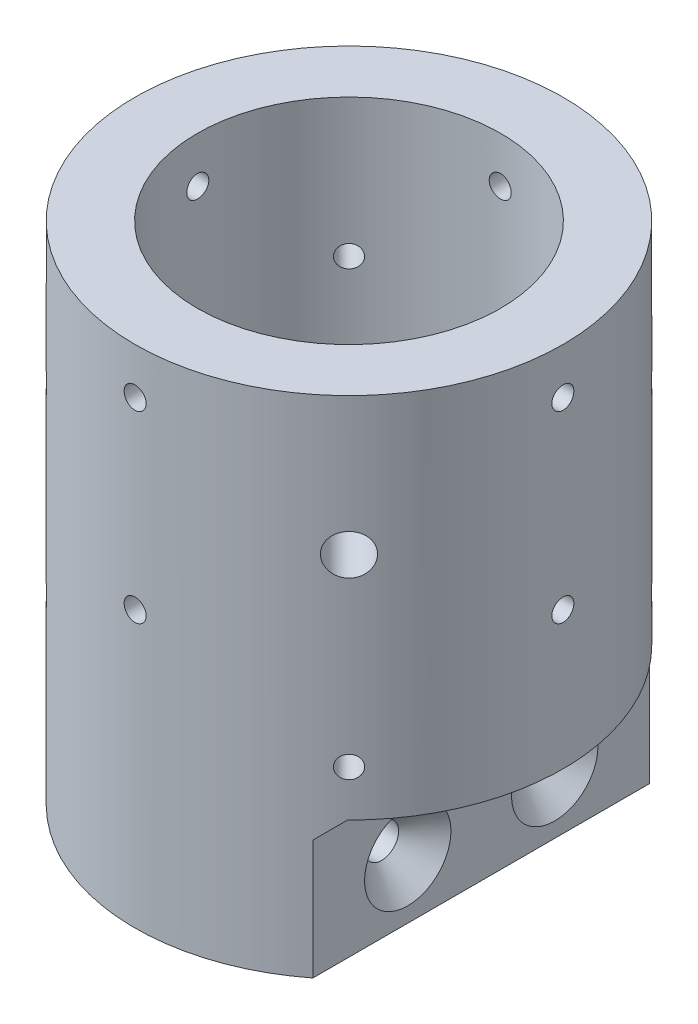
SolidWorks part; units mm, degrees
ref_plane "Спереди" through (0, 0, 0) normal (0, 0, 1) x (1, 0, 0)
ref_plane "Сверху" through (0, 0, 0) normal (0, 1, 0) x (1, 0, 0)
ref_plane "Справа" through (0, 0, 0) normal (1, 0, 0) x (0, 0, -1)
sketch "Эскиз1" plane through (0, 0, 0) normal (0, 1, 0) x (1, 0, 0)
  circle A0 centre (0, 0) radius 23.3
  dimension "D1" = 46.6
extrude "Бобышка-Вытянуть1" add sketch "Эскиз1" along normal blind 5
sketch "Эскиз2" plane through (0, 5, 0) normal (0, 1, 0) x (1, 0, 0)
  circle A0 centre (0, 0) radius 23.3
  circle A1 centre (0, 0) radius 16.5
  circle A2 centre (0, 0) radius 23.3 construction
  dimension "D1" = 33
  dimension "D2" = 0
extrude "Бобышка-Вытянуть2" add sketch "Эскиз2" along normal blind 35
chamfer "Фаска8" distance 2 angle 45 1 edges at (0, 5, 16.5)
sketch "Эскиз3" plane through (0, 0, 0) normal (1, 0, 0) x (0, 0, -1)
  line L0 (-23.3, 20) -> (28.0263, 20) construction
  line L1 (-23.3, 40) -> (-23.3, 0) construction
  line L2 (16.5, 40) -> (-16.5, 40) construction
  circle A1 centre (0, 35) radius 1.2
  dimension "D1" = 2.4
  dimension "D2" = 5
extrude "Вырез-Вытянуть1" cut sketch "Эскиз3" against normal through all
ref_plane "Плоскость1" through (0, 0, 0) normal (0.7071, 0, 0.7071) x (0, -1, 0)
sketch "Эскиз4" plane through (0, 0, 0) normal (0.7071, 0, 0.7071) x (0, -1, 0)
  line L0 (-20, 23.3) -> (-20, -30.0625) construction
  line L1 (0, 23.3) -> (-40, 23.3) construction
  line L3 (0, -23.3) -> (0, 23.3) construction
  circle A1 centre (-5, 0) radius 1.2
  dimension "D1" = 5
  dimension "D2" = 2.4
extrude "Вырез-Вытянуть2" cut sketch "Эскиз4" against normal through all from offset 16.3 offset against normal yes
pattern_circular "Круговой массив1" count 4 over 360 about axis through (0, 5, 0) along (0, -1, 0) of "Вырез-Вытянуть2"
pattern_circular "Круговой массив2" count 4 over 360 about axis through (0, 5, 0) along (0, -1, 0) of "Вырез-Вытянуть1"
pattern_linear "Линейный массив3" count 2 spacing 20 along (0, 1, 0) of "Круговой массив1"
pattern_linear "Линейный массив4" count 2 spacing 20 along (0, -1, 0) of "Круговой массив2"
sketch "Эскиз12" plane through (0, 0, 0) normal (0, -1, 0) x (1, 0, 0)
  line L1 (14.3923, 18.3235) -> (14.3923, -18.3235)
  line L20 (0, 15) -> (-2.7835, 17.7835)
  line L21 (-2.7835, -17.7835) -> (0, -15)
  line L22 (0, -15) -> (0, 15)
  line L23 (0, 15) -> (-2.7835, 17.7835)
  line L24 (-2.7835, -17.7835) -> (0, -15)
  line L25 (0, -15) -> (0, 15)
  circle A6 centre (0, 0) radius 23.3 construction
  arc A7 (14.3923, 18.3235) -> (14.3923, -18.3235) centre (0, 0) ccw
  arc A13 (-2.7835, 17.7835) -> (-2.7835, -17.7835) centre (0, 0) ccw
  arc A14 (-2.7835, 17.7835) -> (-2.7835, -17.7835) centre (0, 0) ccw
  dimension "D1" = 0
extrude "Бобышка-Вытянуть3" add sketch "Эскиз12" along normal blind 15 contours L1 region at (13.7929, 0, 0)
sketch "Эскиз13" plane through (0, -15, 0) normal (0, -1, 0) x (1, 0, 0)
  line L14 (-2.6786, -18.1029) -> (0.3, -15.1243)
  line L15 (0.3, 15.1243) -> (-2.6786, 18.1029)
  line L16 (0.3, -15.1243) -> (0.3, 15.1243)
  line L17 (-2.6786, -18.1029) -> (0.3, -15.1243)
  line L18 (0.3, 15.1243) -> (-2.6786, 18.1029)
  line L19 (0.3, -15.1243) -> (0.3, 15.1243)
  arc A5 (-2.6786, 18.1029) -> (-2.6786, -18.1029) centre (0, 0) ccw
  arc A6 (-2.6786, 18.1029) -> (-2.6786, -18.1029) centre (0, 0) ccw
  dimension "D1" = 0.3
extrude "Вырез-Вытянуть10" cut sketch "Эскиз13" against normal up to surface (15 mm away) up to face at (18.8461, 0, 0)
chamfer "Фаска4" distance 2 angle 45 1 edges at (14.3923, 0, 0)
chamfer "Фаска6" distance 2 angle 45 4 edges at (-1.1893, 0, -16.6136) (-18.3, 0, 0) (0.3, 0, 0) (-1.1893, 0, 16.6136)
chamfer "Фаска7" distance 2 angle 45 4 edges at (-1.1893, -15, -16.6136) (-18.3, -15, 0) (-1.1893, -15, 16.6136) (0.3, -15, 0)
hole_wizard "Зенковка для винта с полупотайной головкой M41" positions "Эскиз14" profile "Эскиз15" countersink size "M4" standard "ISO" end condition through all
sketch "Эскиз14" plane through (14.3923, -676.2045, -24.0267) normal (1, 0, 0) x (0, 0.0202, -0.9998)
  line L0 (-10.4265, 674.5519) -> (-10.6887, 661.5545) construction
  line L4 (-10.5576, 668.0532) -> (-20.4413, 668.0532) construction
  line L5 (-20.4413, 668.0532) -> (-1.8045, 668.0532) construction
  point P0 (-18.5576, 668.0532)
  point P19 (-2.5641, 667.7306)
sketch "Эскиз15" plane through (14.3923, -8.6613, 7.9984) normal (0, 1, 0) x (0, 0, -1)
  line L0 (0, 0) -> (0, 37.6923)
  line L1 (0, 37.6923) -> (1.85, 37.6923)
  line L2 (1.85, 37.6923) -> (1.85, 2.85)
  line L3 (1.85, 2.85) -> (4.7, 0)
  line L4 (4.7, 0) -> (0, 0)
  line L5 (-1.85, 2.85) -> (-4.7, 0) construction
  line L6 (0, -6.35) -> (0, 107.95) construction
  dimension "Диаметр сквозного отверстия" = 3.7
  dimension "Глубина сквозного отверстия" = 37.6923
  dimension "Диаметр передней зенковки" = 9.4
  dimension "Угол передней зенковки" = 90
sketch "Эскиз17" plane through (0, -15, 0) normal (0, -1, 0) x (1, 0, 0)
  circle A0 centre (5.3288, 0) radius 2.5
extrude "Вырез-Вытянуть11" cut sketch "Эскиз17" against normal blind 86
ref_plane "Плоскость2" through (0, 0, 0) normal (-0.7071, 0, -0.7071) x (-0.7071, 0, 0.7071)
sketch "Эскиз18" plane through (0, 0, 0) normal (-0.7071, 0, -0.7071) x (-0.7071, 0, 0.7071)
  circle A0 centre (0, 25) radius 1.2 construction
  circle A1 centre (0, 25) radius 1.2
  circle A2 centre (0, 25) radius 2.2
extrude "Вырез-Вытянуть12" cut sketch "Эскиз18" against normal blind 86
